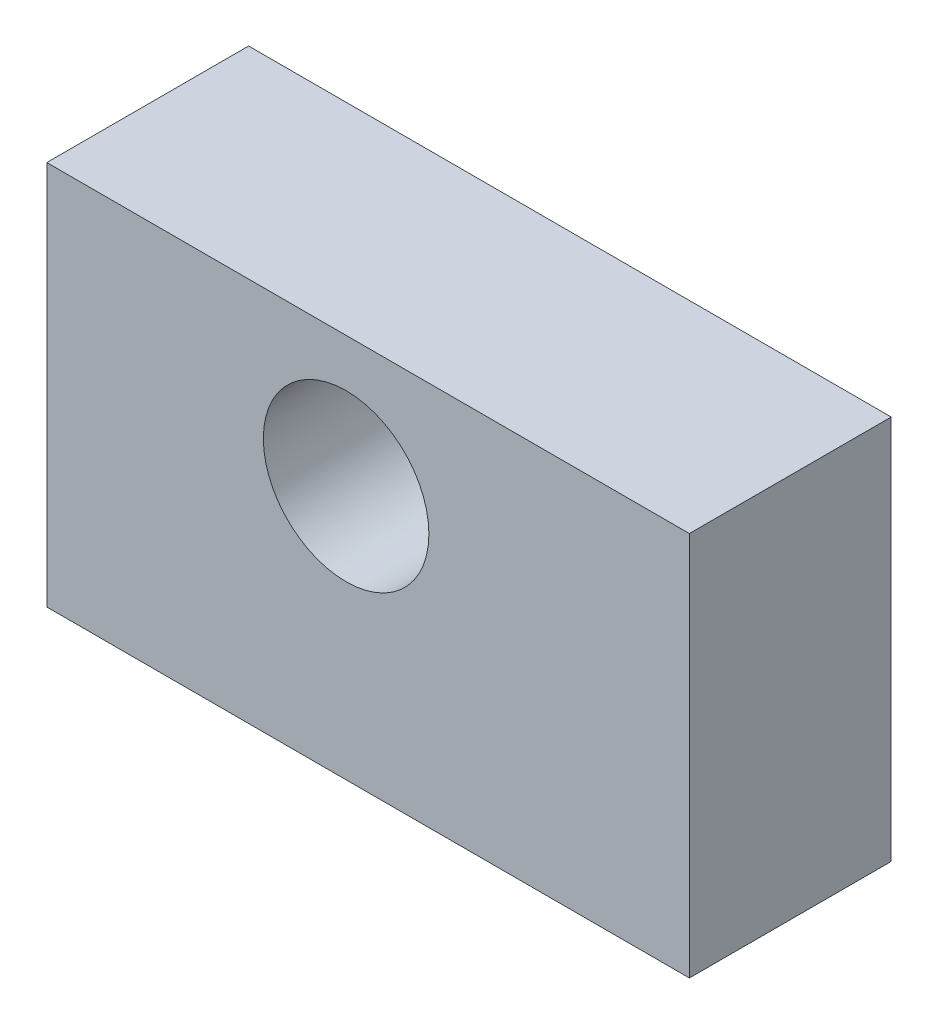
SolidWorks part; units mm, degrees
material "Al-Aly 7075-T7351 Plate per AMS 4078"
ref_plane "Z Plane" through (0, 0, 0) normal (0, 0, 1) x (1, 0, 0)
ref_plane "Y Plane" through (0, 0, 0) normal (0, 1, 0) x (1, 0, 0)
ref_plane "X Plane" through (0, 0, 0) normal (1, 0, 0) x (0, 0, -1)
ref_axis "X Axis" through (-88.99, 0, 0) along (1, 0, 0)
ref_axis "Z Axis" through (0, 0, -88.99) along (0, 0, 1)
ref_axis "Y Axis" through (0, 55, 0) along (0, -1, 0)
sketch "Sketch1" plane through (0, 0, 0) normal (0, 0, 1) x (1, 0, 0)
  line L1 (-80.8622, -48.4364) -> (80.8622, -48.4364)
  line L2 (-80.8622, -48.4364) -> (-80.8622, 48.4364)
  line L3 (-80.8622, 48.4364) -> (80.8622, 48.4364)
  line L4 (80.8622, -48.4364) -> (80.8622, 48.4364)
  line L5 (-80.8622, -48.4364) -> (80.8622, 48.4364) construction
  line L6 (-80.8622, 48.4364) -> (80.8622, -48.4364) construction
  point P0 (0, 0)
extrude "Boss-Extrude1" add sketch "Sketch1" along normal blind 50.8
sketch "Sketch2" plane through (0, 0, 50.8) normal (0, 0, 1) x (1, 0, 0)
  circle A0 centre (-5.5257, 15.5605) radius 20.831
extrude "Cut-Extrude1" cut sketch "Sketch2" against normal through all contours A0
